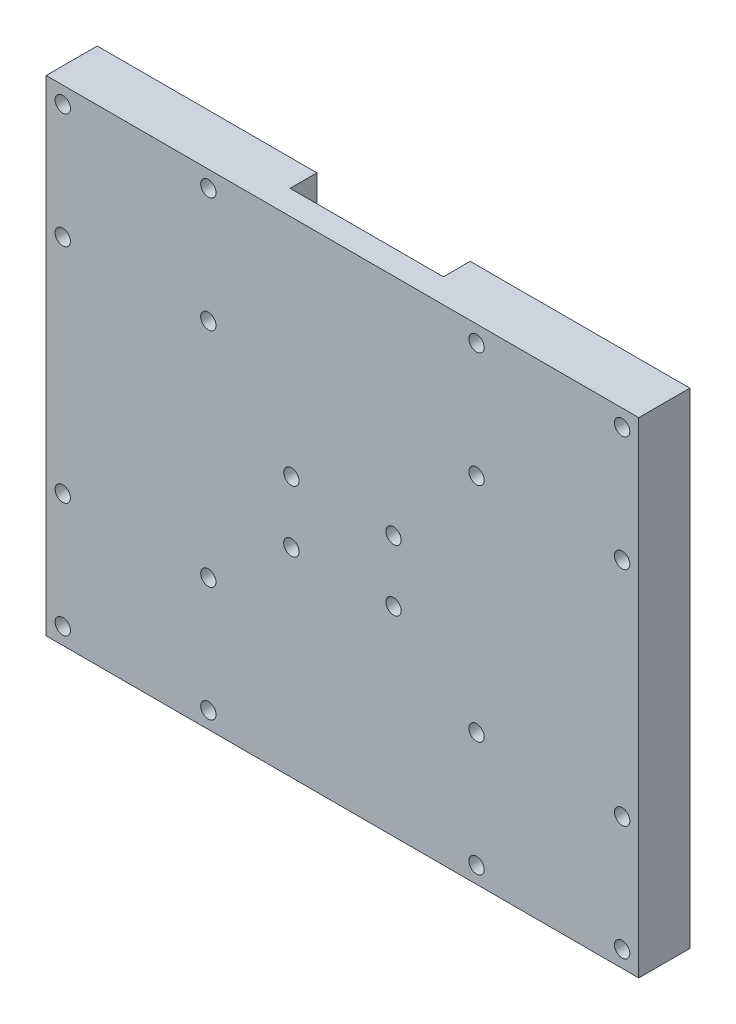
SolidWorks part; units mm, degrees
ref_plane "Piano frontale" through (0, 0, 0) normal (0, 0, 1) x (1, 0, 0)
ref_plane "Piano superiore" through (0, 0, 0) normal (0, 1, 0) x (1, 0, 0)
ref_plane "Piano destro" through (0, 0, 0) normal (1, 0, 0) x (0, 0, -1)
sketch "Schizzo1" plane through (0, 0, 0) normal (0, 0, 1) x (1, 0, 0)
  line L1 (116, -95) -> (-116, -95)
  line L2 (116, -95) -> (116, 95)
  line L3 (116, 95) -> (-116, 95)
  line L4 (-116, -95) -> (-116, 95)
  line L5 (116, -95) -> (-116, 95) construction
  line L6 (116, 95) -> (-116, -95) construction
  point P0 (0, 0)
  dimension "D1" = 232
  dimension "D2" = 190
extrude "Estrusione-Estrusione1" add sketch "Schizzo1" along normal blind 20
sketch "Schizzo3" plane through (0, 0, 20) normal (0, 0, 1) x (1, 0, 0)
  line L0 (20, 7) -> (-20, 7) construction
  line L1 (-20, 7) -> (20, -17) construction
  line L2 (20, -17) -> (20, 7) construction
  line L3 (20, 7) -> (-20, -17) construction
  line L4 (-20, -17) -> (-20, 7) construction
  line L5 (-20, -17) -> (20, -17) construction
  circle A8 centre (20, 7) radius 3
  circle A9 centre (-20, 7) radius 3
  circle A10 centre (-20, -17) radius 3
  circle A11 centre (20, -17) radius 3
  circle A14 centre (-109.5, 88.5) radius 3
  circle A15 centre (-52.5, 88.5) radius 3
  circle A18 centre (-109.5, 43.5) radius 3
  circle A19 centre (-52.5, 43.5) radius 3
  circle A24 centre (-109.5, -88.5) radius 3
  circle A25 centre (-109.5, -43.5) radius 3
  circle A26 centre (-52.5, -88.5) radius 3
  circle A27 centre (-52.5, -43.5) radius 3
  point P21 (0, -5)
  dimension "D1" = 40
  dimension "D2" = 24
extrude "Taglio-Estrusione1" cut sketch "Schizzo3" against normal through all
sketch "Schizzo4" plane through (0, 95, 0) normal (0, 1, 0) x (1, 0, 0)
  line L0 (116, 0) -> (-116, 0) construction
  line L1 (30, 0) -> (-30, 0)
  line L2 (30, 0) -> (30, -10.5)
  line L3 (30, -10.5) -> (-30, -10.5)
  line L4 (-30, 0) -> (-30, -10.5)
  dimension "D1" = 10.5
extrude "Taglio-Estrusione2" cut sketch "Schizzo4" against normal through all
mirror "Specchia1" about plane through (0, 0, 0) normal (1, 0, 0) of "Taglio-Estrusione1"
